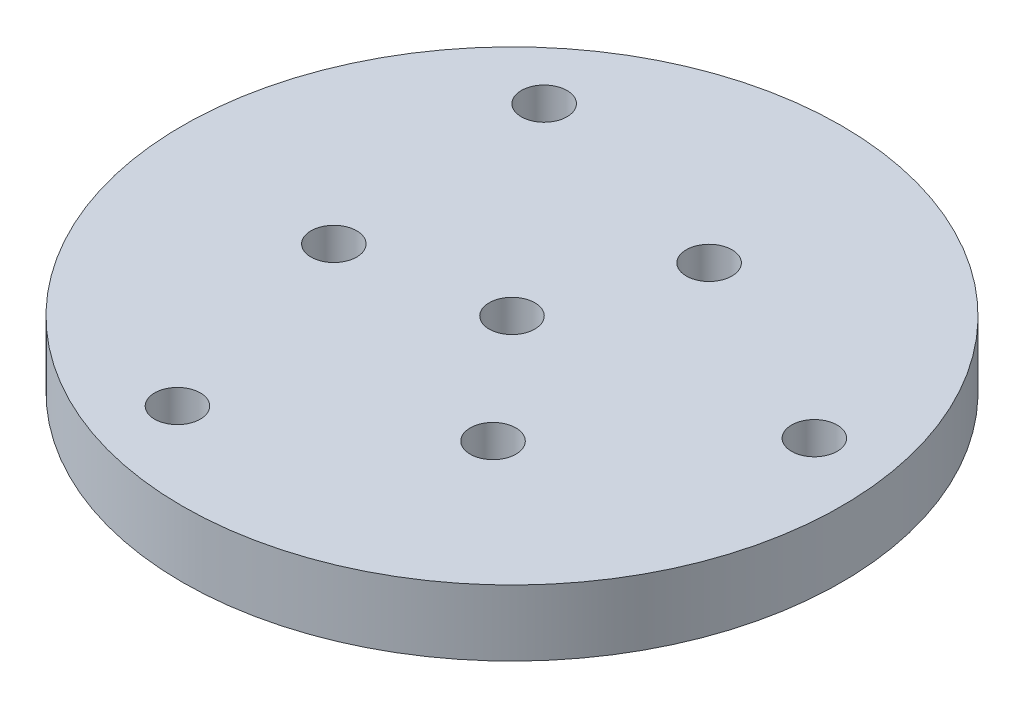
SolidWorks part; units mm, degrees
material "6061-T6 (SS)"
ref_plane "Front Plane" through (0, 0, 0) normal (0, 0, 1) x (1, 0, 0)
ref_plane "Top Plane" through (0, 0, 0) normal (0, 1, 0) x (1, 0, 0)
ref_plane "Right Plane" through (0, 0, 0) normal (1, 0, 0) x (0, 0, -1)
sketch "Sketch1" plane through (0, 0, 0) normal (0, 1, 0) x (1, 0, 0)
  circle A0 centre (0, 0) radius 47.625
  circle A1 centre (0, 0) radius 3.3
  circle A2 centre (0, 25.4) radius 1.5875 construction
  dimension "D1" = 95.25
  dimension "D2" = 6.6
  dimension "D3" = 3.175
  dimension "D4" = 25.4
extrude "Boss-Extrude1" add sketch "Sketch1" along normal mid plane 9.525
ref_plane "Plane1" through (0, 0, 50.8) normal (0, 0, 1) x (1, 0, 0)
sketch "Sketch2" plane through (0, 0, 50.8) normal (0, 0, 1) x (1, 0, 0)
  circle A0 centre (0, 0) radius 1.3526
  dimension "D1" = 2.7051
extrude "Cut-Extrude1" [suppressed] cut sketch "Sketch2" against normal blind 12.7
sketch "Sketch3" plane through (0, 0, 0) normal (0, 0, 1) x (1, 0, 0)
  line L0 (0, 4.7625) -> (0, -4.7625)
  line L1 (47.625, 4.7625) -> (-47.625, 4.7625) construction
  line L2 (-47.625, -4.7625) -> (47.625, -4.7625) construction
pattern_circular "CirPattern1" [suppressed] count 4 over 360 about axis through (0, 4.7625, 0) along (0, -1, 0) of bodies 102
sketch "Sketch4" plane through (0, 4.7625, 0) normal (0, 1, 0) x (1, 0, 0)
  line L0 (0, 0) -> (0, -35.975) construction
  line L1 (-12.9007, -35.4443) -> (0, 0) construction
  line L2 (0, 0) -> (14.286, -17.0253) construction
  circle A0 centre (-12.9007, -35.4443) radius 3.3
  circle A1 centre (-24.2453, 28.8944) radius 3.3
  circle A2 centre (37.146, 6.5498) radius 3.3
  circle A3 centre (14.286, -17.0253) radius 3.3
  circle A4 centre (-21.8874, -3.8593) radius 3.3
  circle A5 centre (7.6014, 20.8847) radius 3.3
  point P12 (0, 0)
  point P19 (0, 0)
  dimension "D1" = 6.6
  dimension "D7" = 6.6
  dimension "D2" = 37.719
  dimension "D3" = 20
  dimension "D5" = 60
  dimension "D6" = 22.225
  dimension "D4" = 3
  dimension "D8" = 3
extrude "Cut-Extrude2" cut sketch "Sketch4" against normal through all
equation "\"Body_Tube_OD\"= 4.024in"
equation "\"Body_Tube_ID\"= 3.90in"
equation "\"SS_Fwd_Bulkhead_OD\"=3.75"
equation "\"D1@Sketch1\"=\"SS_Fwd_Bulkhead_OD\""
equation "\"Bodytube_OD\" = 6.17in"
equation "\"Bodytube_ID\" = 5.998in"
equation "\"Motor_OD\" = 4in"
equation "\"Fwd_Tube_Length\" = 40in"
equation "\"Mid_Tube_Length\" = 1in"
equation "\"Mid_Coupler_Length\" = 13in"
equation "\"Aft_Section_Length\"= 39in"
equation "\"AB_Coupler_OD_Length\"= 1in"
equation "\"AB_Coupling_Section_Length\"= 0.375in"
equation "\"AB_Coupler_Length\"= \"AB_Coupler_OD_Length\" + \"AB_Coupling_Section_Length\" * 2"
equation "\"Cutout_Angle\" = 80"
equation "\"AB_Paddle_Height\" = 0.375in"
equation "\"AB_Coupler_Num_Screws\"= 6"
equation "\"AB_BKHD_Thickness\" = 0.375in"
equation "\"AB_Mount_From_Bottom\" = 23.175in"
equation "\"Num_Cutouts\" = 3"
equation "\"AB_Coupler_OD\"= 6.17in"
equation "\"AB_Coupler_ID\"= 5.75in"
equation "\"AB_Coupler_Surface_Diameter\"= 5.998in"
equation "\"AB_Coupling_Screw_Diameter\"= 0.1065in"
equation "\"AB_Central_Bushing_Length\" = .75in"
equation "\"Lead_Screw_Dist\" = 2.25in"
equation "\"Lead_Screw_Diam\" = 11mm"
equation "\"Lead_Screw_Length\" = (\"Mid_Coupler_Length\" + 2*0.375in + 2*0.5in)"
equation "\"Paddle_Pin_Offset\" = .25in"
equation "\"Paddle_Pin_Radius\" = 2.25in"
equation "\"SS_Paddle_Pin_Radius\" = 2.25*0.66in"
equation "\"Paddle_Gear_OD\" = 3.2in"
equation "\"Drive_Gear_OD\" = 1.7in"
equation "\"Fwd_BKHD_From_Top\" = 18in"
equation "\"Fin_Thickness\"= .118in"
equation "\"Guiderail_Cutout_Diameter\"= 1.5in"
equation "\"DB9_Hole_Dist\" = 25mm"
equation "\"DB9_Relief_Width\" = 0.47in"
equation "\"DB9_Relief_Hole_Offset\" = 0.09in"
equation "\"Airbrakes_Wire_Hole_Dia\" = .25in"
equation "\"Airbrakes_Wire_Hole_Dist\" = 1.1in"
equation "\"Servo_Gear_Offset\" = 0.5in"
